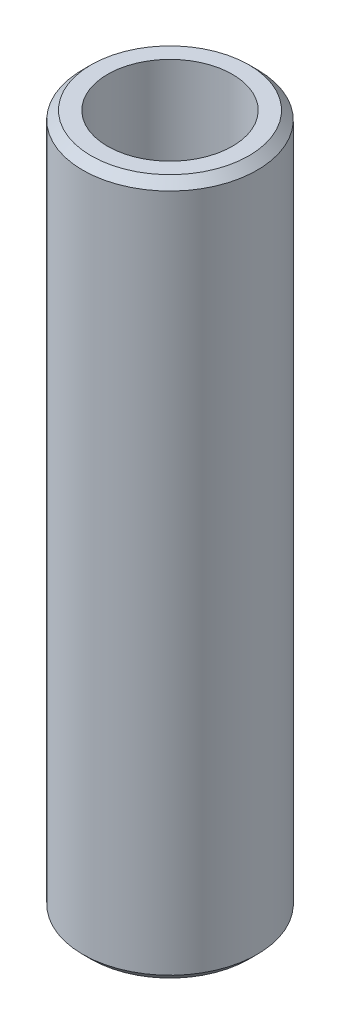
SolidWorks part; units mm, degrees
ref_plane "Front Plane" through (0, 0, 0) normal (0, 0, 1) x (1, 0, 0)
ref_plane "Top Plane" through (0, 0, 0) normal (0, 1, 0) x (1, 0, 0)
ref_plane "Right Plane" through (0, 0, 0) normal (1, 0, 0) x (0, 0, -1)
sketch "Sketch1" plane through (0, 0, 0) normal (0, 1, 0) x (1, 0, 0)
  circle A0 centre (0, 0) radius 32.5
  dimension "SHAFT_OD" = 65
extrude "Boss-Extrude1" add sketch "Sketch1" along normal blind 259.3356
sketch "Sketch2" plane through (0, 0, 0) normal (0, 1, 0) x (1, 0, 0)
  circle A0 centre (0, 0) radius 23.2556
  dimension "BORE_D" = 46.5112
extrude "Cut-Extrude1" cut sketch "Sketch2" along normal through all
chamfer "Chamfer1" distance 3.0995 angle 45 2 edges at (0, 259.3356, 32.5) (0, 0, 32.5)
